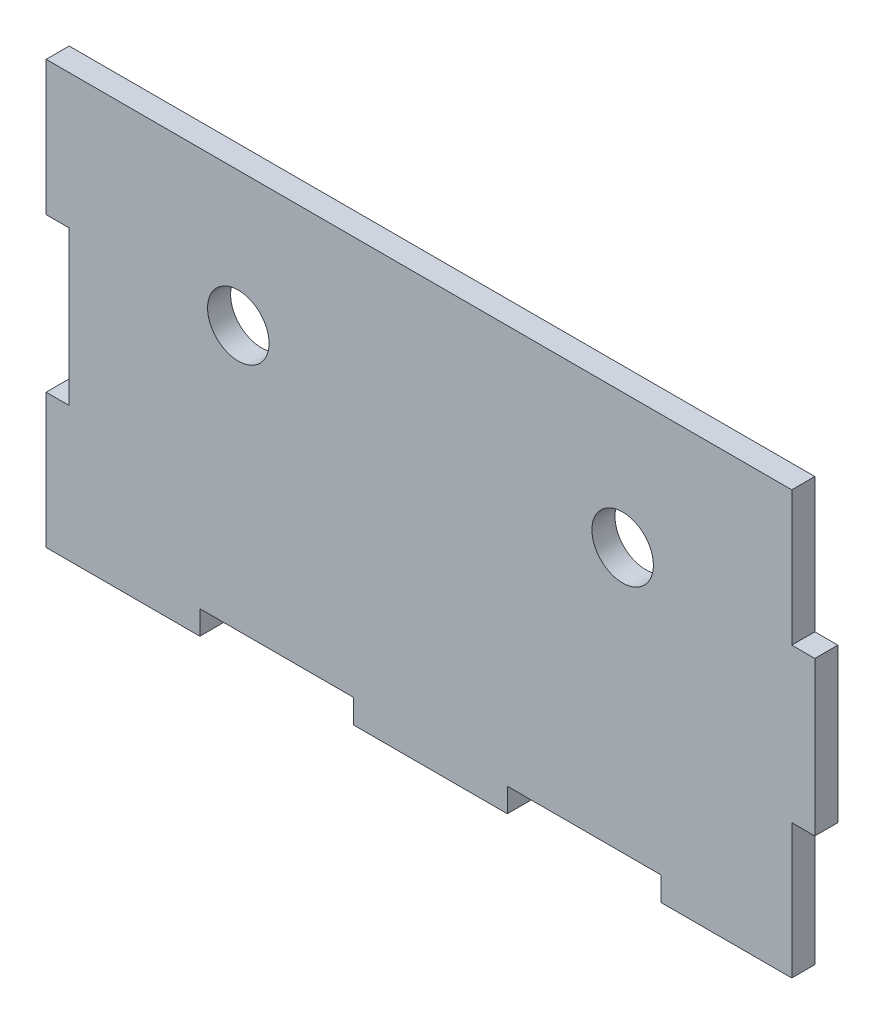
SolidWorks part; units mm, degrees
ref_plane "Front Plane" through (0, 0, 0) normal (0, 0, 1) x (1, 0, 0)
ref_plane "Top Plane" through (0, 0, 0) normal (0, 1, 0) x (1, 0, 0)
ref_plane "Right Plane" through (0, 0, 0) normal (1, 0, 0) x (0, 0, -1)
sketch "Sketch1" plane through (0, 0, 0) normal (0, 0, 1) x (1, 0, 0)
  line L0 (-50, -27.5) -> (-50, -10)
  line L1 (-50, -27.5) -> (50, -27.5)
  line L2 (-50, -27.5) -> (-50, 27.5)
  line L3 (-50, 27.5) -> (50, 27.5)
  line L4 (50, -27.5) -> (50, 27.5)
  line L5 (-50, -27.5) -> (50, 27.5) construction
  line L6 (-50, 27.5) -> (50, -27.5) construction
  line L7 (-50, -10) -> (-47, -10)
  line L8 (-47, -10) -> (-47, 10)
  line L9 (-47, 10) -> (-50, 10)
  line L10 (-50, 10) -> (-50, 27.5)
  line L11 (50, -10) -> (47, -10)
  line L12 (47, -10) -> (47, -27.5)
  line L13 (50, 10) -> (47, 10)
  line L14 (47, 10) -> (47, 27.5)
  line L15 (-50, -27.5) -> (-30, -27.5)
  line L16 (-30, -27.5) -> (-30, -24.3935)
  line L17 (-30, -24.3935) -> (-10, -24.3935)
  line L18 (-10, -24.3935) -> (-10, -27.5)
  line L19 (-10, -27.5) -> (10, -27.5)
  line L20 (10, -27.5) -> (10, -24.3935)
  line L21 (10, -24.3935) -> (30, -24.3935)
  line L22 (30, -24.3935) -> (30, -27.5)
  circle A0 centre (-25, 10) radius 4
  circle A1 centre (25, 10) radius 4
  point P0 (0, 0)
  dimension "D12" = 8
  dimension "D15" = 8
  dimension "D1" = 55
  dimension "D2" = 17.5
  dimension "D3" = 17.5
  dimension "D4" = 3
  dimension "D5" = 3
  dimension "D6" = 3
  dimension "D7" = 100
  dimension "D8" = 20
  dimension "D9" = 20
  dimension "D10" = 20
  dimension "D11" = 20
  dimension "D13" = 25
  dimension "D14" = 17.5
  dimension "D16" = 17.5
  dimension "D17" = 25
extrude "Boss-Extrude1" add sketch "Sketch1" along normal blind 3 contours L13 L14 L3 L2 L9 L8 L7 L0 L1 L12 L11 L4 region at (-0.4271, 0.4342, 0)
